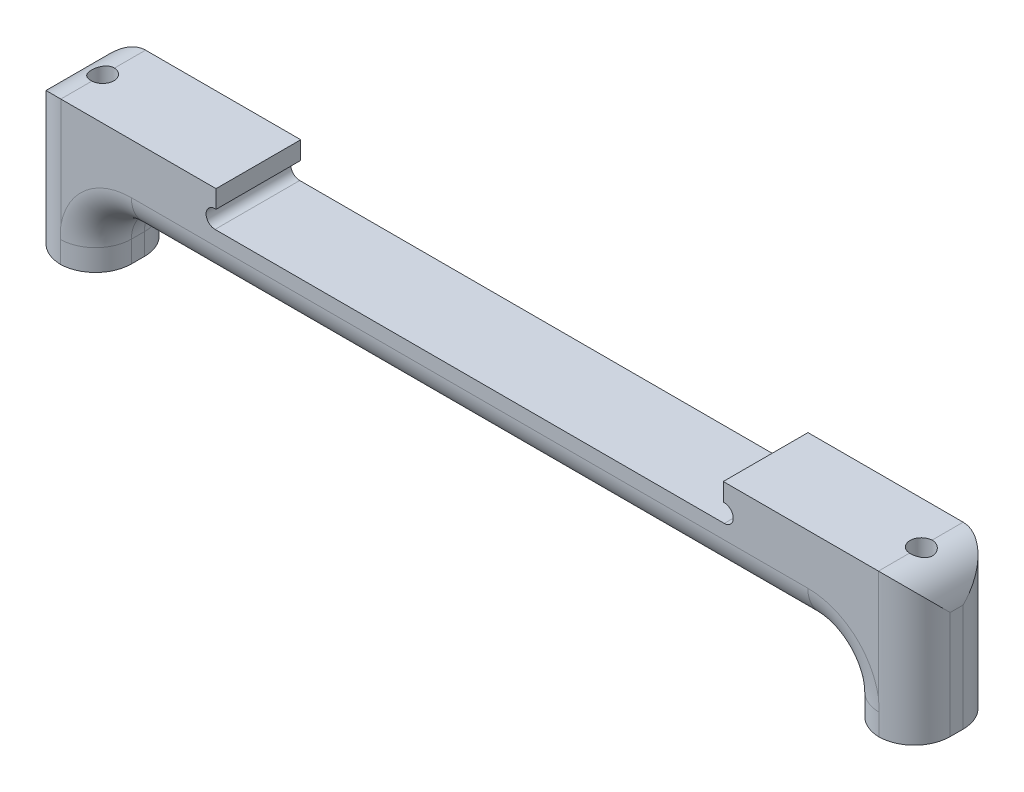
SolidWorks part; units mm, degrees
material "ABS"
ref_plane "Front" through (0, 0, 0) normal (0, 0, 1) x (1, 0, 0)
ref_plane "Top" through (0, 0, 0) normal (0, 1, 0) x (1, 0, 0)
ref_plane "Right" through (0, 0, 0) normal (1, 0, 0) x (0, 0, -1)
ref_axis "Axis1" through (0, 0, 55) along (0, 0, -1)
sketch "Sketch1" plane through (0, 0, 0) normal (0, 0, 1) x (1, 0, 0)
  line L0 (-28.9941, 0) -> (28.9941, 0) construction
  line L1 (-31.4941, 0) -> (-26.4941, 0)
  line L2 (-26.4941, 0) -> (-26.4941, 1.524)
  line L3 (-23.9541, 4.064) -> (23.9541, 4.064)
  line L4 (26.4941, 1.524) -> (26.4941, 0)
  line L5 (26.4941, 0) -> (31.4941, 0)
  line L6 (-31.4941, 0) -> (-31.4941, 10.1561)
  line L7 (-31.4941, 10.1561) -> (-17.9634, 10.1561)
  line L8 (-17.9634, 10.1561) -> (-17.9634, 8.8861)
  line L9 (-18.034, 7.62) -> (18.034, 7.62)
  line L10 (0, 0) -> (0, 15.2653) construction
  line L11 (31.4941, 0) -> (31.4941, 10.1561)
  line L12 (31.4941, 10.1561) -> (17.9634, 10.1561)
  line L13 (17.9634, 10.1561) -> (17.9634, 8.8861)
  arc A0 (-17.9634, 8.8861) -> (-18.034, 7.62) centre (-18.034, 8.255) ccw
  arc A1 (17.9634, 8.8861) -> (18.034, 7.62) centre (18.034, 8.255) cw
  arc A2 (26.4941, 1.524) -> (23.9541, 4.064) centre (23.9541, 1.524) ccw
  arc A3 (-23.9541, 4.064) -> (-26.4941, 1.524) centre (-23.9541, 1.524) ccw
  point P4 (0, 0)
  point P8 (-28.9941, 0)
  point P20 (0, 7.62)
  point P26 (28.9941, 0)
  dimension "D3" = 0.635
  dimension "D9" = 2.54
  dimension "D1" = 57.9882
  dimension "D2" = 5
  dimension "D4" = 36.068
  dimension "D5" = 4.064
  dimension "D6" = 1.27
  dimension "D7" = 13.5307
  dimension "D8" = 3.556
extrude "Boss-Extrude1" add sketch "Sketch1" along normal blind 6
hole_wizard "M2x0.4 Tapped Hole1" positions "Sketch2" profile "Sketch3" tap size "M2x0.4" standard "ANSI Metric" end condition up to next
sketch "Sketch2" plane through (0, 0, 0) normal (0, -1, 0) x (-1, 0, 0)
  line L0 (28.9941, -6) -> (28.9941, 0) construction
  line L1 (31.4941, -6) -> (26.4941, -6) construction
  line L2 (31.4941, 0) -> (26.4941, 0) construction
  line L4 (-28.9941, -6) -> (-28.9941, 0) construction
  line L5 (-26.4941, -6) -> (-31.4941, -6) construction
  line L7 (-26.4941, 0) -> (-31.4941, 0) construction
  point P0 (28.9941, -3)
  point P2 (-28.9941, -3)
  point P18 (-28.9941, 0)
  point P21 (-28.9941, -3)
  point P22 (28.9941, -3)
sketch "Sketch3" plane through (-28.9941, 0, 3) normal (1, 0, 0) x (0, 0, -1)
  line L0 (0, 0) -> (0, 10.1561)
  line L1 (0, 10.1561) -> (0.8, 10.1561)
  line L2 (0.8, 10.1561) -> (0.8, 0)
  line L5 (0.8, 0) -> (0, 0)
  line L11 (0, -6.35) -> (0, 107.95) construction
  dimension "Thru Tap Drill Dia." = 1.6
  dimension "Thru Tap Drill Depth" = 10.1561
cosmetic thread "Hole Thread1" parameters "D2"=2
cosmetic thread "Hole Thread2" parameters "D2"=2
fillet "Fillet1" radius 2.54 16 edges at (-26.4941, 0.762, 0) (-25.7502, 3.3201, 0) (26.4941, 0.762, 0) (25.7502, 3.3201, 0) (-26.4941, 0.762, 6) (-25.7502, 3.3201, 6) (0, 4.064, 6) (25.7502, 3.3201, 6) (-31.4941, 5.078, 0) (-31.4941, 5.078, 6) (31.4941, 5.078, 0) (31.4941, 5.078, 6) (0, 4.064, 0) (26.4941, 0.762, 6) (31.4941, 10.1561, 3) (-31.4941, 10.1561, 3)
